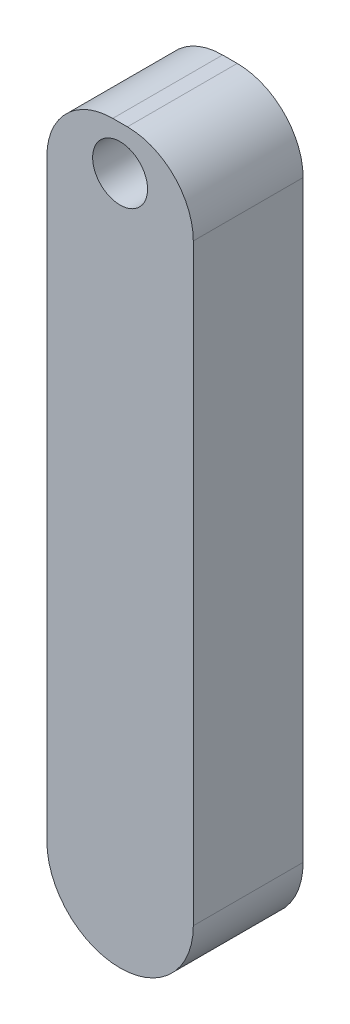
SolidWorks part; units mm, degrees
ref_plane "Front" through (0, 0, 0) normal (0, 0, 1) x (1, 0, 0)
ref_plane "Top" through (0, 0, 0) normal (0, 1, 0) x (1, 0, 0)
ref_plane "Right" through (0, 0, 0) normal (1, 0, 0) x (0, 0, -1)
sketch "Sketch2" plane through (0, 0, 0) normal (0, 0, 1) x (1, 0, 0)
  line L1 (-20, -100) -> (20, -100)
  line L2 (-20, -100) -> (-20, 100)
  line L3 (-20, 100) -> (20, 100)
  line L4 (20, -100) -> (20, 100)
  line L5 (-20, -100) -> (20, 100) construction
  line L6 (-20, 100) -> (20, -100) construction
  point P1 (0, 0)
  dimension "D1" = 200
  dimension "D2" = 40
extrude "Boss-Extrude1" add sketch "Sketch2" along normal blind 30
sketch "Sketch3" plane through (0, 0, 0) normal (0, 0, -1) x (-1, 0, 0)
  line L0 (20, -100) -> (-20, -100) construction
  circle A0 centre (0, -90) radius 2
  dimension "D1" = 4
  dimension "D2" = 10
extrude "Cut-Extrude1" cut sketch "Sketch3" against normal blind 10
fillet "Fillet1" radius 20 2 edges at (20, -100, 15) (-20, -100, 15)
sketch "Sketch5" plane through (0, 0, 30) normal (0, 0, 1) x (1, 0, 0)
  line L0 (20, -80) -> (20, 100) construction
  line L1 (20, 100) -> (-20, 100) construction
  circle A0 centre (0, 88) radius 7.5
  point P4 (0, 0)
  point P6 (-3.3615, 88.2246)
  dimension "D1" = 15
  dimension "D2" = 20
  dimension "D3" = 12
extrude "Cut-Extrude3" cut sketch "Sketch5" against normal blind 20
fillet "Fillet2" radius 18 2 edges at (20, 100, 15) (-20, 100, 15)
sketch "Sketch6" plane through (-20, 0, 0) normal (-1, 0, 0) x (0, 0, 1)
  line L0 (0, -80) -> (30, -80) construction
  line L1 (10, -80) -> (20, -80)
  line L2 (10, -80) -> (10, 82)
  line L3 (10, 82) -> (20, 82)
  line L4 (20, -80) -> (20, 82)
  line L5 (30, 82) -> (0, 82) construction
  line L6 (20, 82) -> (30, 82) construction
  line L7 (10, 82) -> (0, 82) construction
  dimension "D1" = 10
extrude "Cut-Extrude4" cut sketch "Sketch6" against normal blind 15
sketch "Sketch7" plane through (0, 0, 20) normal (0, 0, -1) x (-1, 0, 0)
  line L0 (20, -80) -> (20, 82) construction
  line L2 (20, 1) -> (15, 1)
  line L3 (20, 1) -> (20, -9)
  line L4 (20, -9) -> (15, -9)
  line L5 (15, 1) -> (15, -9)
  dimension "D1" = 5
  dimension "D2" = 10
extrude "Boss-Extrude2" add sketch "Sketch7" along normal blind 15
